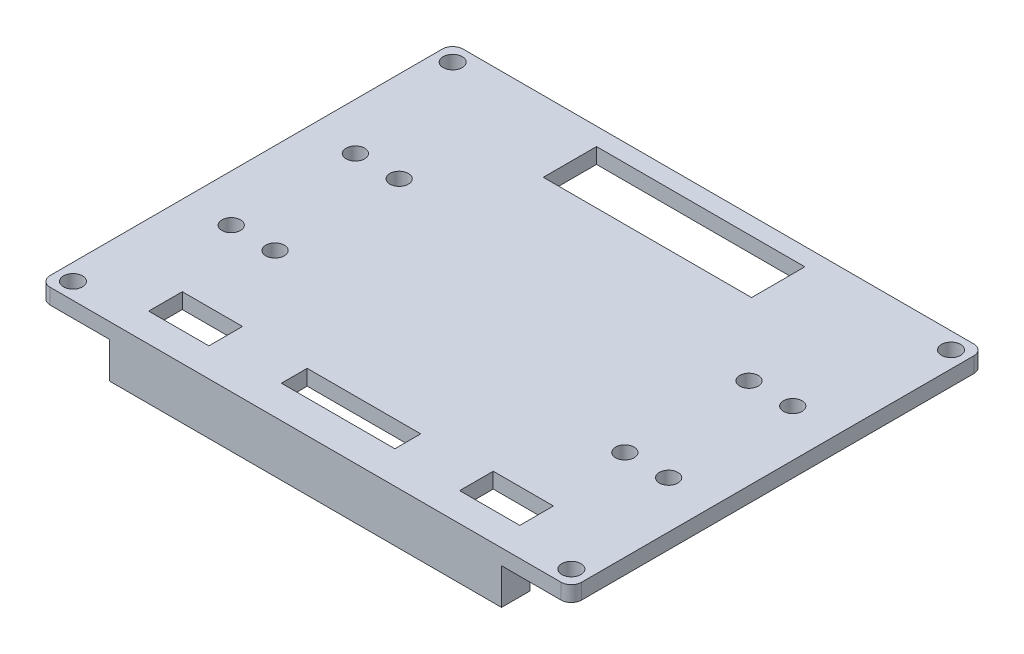
SolidWorks part; units mm, degrees
ref_plane "前视基准面" through (0, 0, 0) normal (0, 0, 1) x (1, 0, 0)
ref_plane "上视基准面" through (0, 0, 0) normal (0, 1, 0) x (1, 0, 0)
ref_plane "右视基准面" through (0, 0, 0) normal (1, 0, 0) x (0, 0, -1)
sketch "草图1" plane through (0, 0, 0) normal (0, 1, 0) x (1, 0, 0)
  line L0 (-51.5, 40) -> (-48.2968, 36.7968) construction
  line L1 (49.5, -40) -> (-49.5, -40)
  line L2 (51.5, -38) -> (51.5, 38)
  line L3 (49.5, 40) -> (-49.5, 40)
  line L4 (-51.5, -38) -> (-51.5, 38)
  line L5 (51.5, -40) -> (-51.5, 40) construction
  line L6 (51.5, 40) -> (-51.5, -40) construction
  line L7 (20.1874, 26.2491) -> (-20.1874, 26.2491)
  line L8 (20.1874, 26.2491) -> (20.1874, 36.5704)
  line L9 (20.1874, 36.5704) -> (-20.1874, 36.5704)
  line L10 (-20.1874, 26.2491) -> (-20.1874, 36.5704)
  line L11 (20.1874, 26.2491) -> (-20.1874, 36.5704) construction
  line L12 (20.1874, 36.5704) -> (-20.1874, 26.2491) construction
  line L13 (0, 31.4098) -> (0, -40) construction
  line L14 (51.5, 0) -> (-51.5, 0)
  line L16 (11, -33.6959) -> (-11, -33.6959)
  line L17 (11, -33.6959) -> (11, -28.6959)
  line L18 (11, -28.6959) -> (-11, -28.6959)
  line L19 (-11, -33.6959) -> (-11, -28.6959)
  line L20 (11, -33.6959) -> (-11, -28.6959) construction
  line L21 (11, -28.6959) -> (-11, -33.6959) construction
  line L26 (24.3014, -27.9372) -> (35.9691, -27.9372)
  line L27 (-24.3014, -34.4545) -> (-35.9691, -34.4545)
  line L31 (-24.3014, -34.4545) -> (-24.3014, -27.9372)
  line L32 (-24.3014, -27.9372) -> (-35.9691, -27.9372)
  line L33 (-35.9691, -34.4545) -> (-35.9691, -27.9372)
  line L34 (-24.3014, -34.4545) -> (-35.9691, -27.9372) construction
  line L35 (-24.3014, -27.9372) -> (-35.9691, -34.4545) construction
  line L36 (35.9691, -34.4545) -> (35.9691, -27.9372)
  line L37 (24.3014, -34.4545) -> (35.9691, -34.4545)
  line L38 (24.3014, -34.4545) -> (24.3014, -27.9372)
  line L39 (-48.2968, 36.7968) -> (-48.2968, -36.7968) construction
  line L47 (-38.1468, 18.3) -> (-38.1468, -18.3) construction
  line L48 (-38.1468, 18.3) -> (-38.1468, 12.03)
  line L49 (-33.9018, 12.03) -> (-42.3918, 12.03)
  circle A0 centre (-48.2968, 36.7968) radius 1.85
  circle A1 centre (48.2968, 36.7968) radius 1.85
  circle A2 centre (48.2968, -36.7968) radius 1.85
  circle A3 centre (-48.2968, -36.7968) radius 1.85
  arc A4 (-49.5, -40) -> (-51.5, -38) centre (-49.5, -38) cw
  arc A5 (49.5, -40) -> (51.5, -38) centre (49.5, -38) ccw
  arc A6 (51.5, 38) -> (49.5, 40) centre (49.5, 38) ccw
  arc A7 (-49.5, 40) -> (-51.5, 38) centre (-49.5, 38) ccw
  circle A8 centre (-42.3918, 12.03) radius 1.8
  circle A9 centre (-33.9018, 12.03) radius 1.8
  circle A10 centre (-33.9018, -12.03) radius 1.8
  circle A11 centre (-42.3918, -12.03) radius 1.8
  circle A12 centre (33.9018, -12.03) radius 1.8
  circle A13 centre (42.3918, -12.03) radius 1.8
  circle A14 centre (33.9018, 12.03) radius 1.8
  circle A15 centre (42.3918, 12.03) radius 1.8
  point P0 (0, 0)
  point P6 (0, 31.4098)
  point P18 (0, 0)
  point P36 (0, -31.1959)
  point P41 (-69.6672, -54.1104)
  point P42 (-30.1353, -31.1959)
  point P54 (-48.2968, 0)
  point P62 (-38.1468, 12.03)
  dimension "D4" = 2
  dimension "D1" = 103
  dimension "D2" = 80
  dimension "D3" = 45
extrude "凸台-拉伸1" add sketch "草图1" along normal blind 3 contours L3 A7 L4 L14 L2 A6 L7 L10 L9 L8 A0 A1 | L1 A5 L2 L14 L4 A4 A3 A2 region at (0, 0, 19.2081) region at (0, 0, -18.6742)
ref_plane "基准面1" through (0, 3, 0) normal (0, 1, 0) x (1, 0, 0)
sketch "草图2" plane through (0, 3, 0) normal (0, 1, 0) x (1, 0, 0)
  line L0 (49.5, -40) -> (-49.5, -40) construction
  line L1 (-37.9691, -34.4545) -> (37.9691, -34.4545)
  line L2 (-37.9691, -34.4545) -> (-37.9691, -40)
  line L3 (-37.9691, -40) -> (37.9691, -40)
  line L4 (37.9691, -34.4545) -> (37.9691, -40)
  dimension "D1" = 2
  dimension "D2" = 2
extrude "凸台-拉伸2" add sketch "草图2" against normal blind 10
